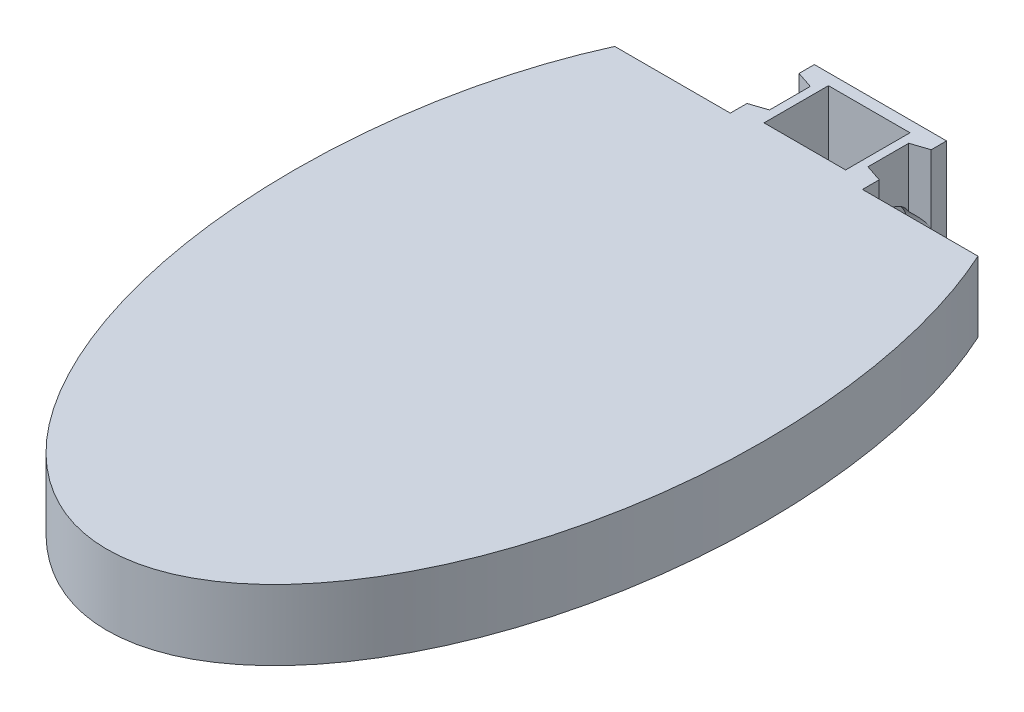
SolidWorks part; units mm, degrees
note: '?' marks a value the reader was unsure of.
ref_plane "Front Plane" through (0, 0, 0) normal (0, 0, 1) x (1, 0, 0)
ref_plane "Top Plane" through (0, 0, 0) normal (0, 1, 0) x (1, 0, 0)
ref_plane "Right Plane" through (0, 0, 0) normal (1, 0, 0) x (0, 0, -1)
sketch "Sketch1" plane through (0, 0, 0) normal (0, 1, 0) x (1, 0, 0)
  line L0 (0, 0) -> (0, 58.7756) construction
  line L1 (0, 0) -> (13.1013, 0) construction
  ellipse E0 centre (0, 0) end of major axis (0, 38.1) minor radius 21.209
  dimension "D1" = 42.418
  dimension "D2" = 76.2
extrude "Boss-Extrude1" add sketch "Sketch1" along normal blind 6.35
sketch "Sketch7" plane through (0, 6.35, 0) normal (0, 1, 0) x (1, 0, 0)
  line L0 (-11.7237, 31.75) -> (11.7237, 31.75)
  ellipse E0 centre (0, 0) end of major axis (0, 38.1) minor radius 21.209 construction
  ellipse E1 centre (0, 0) end of major axis (0, 38.1) minor radius 21.209 (11.7237, 31.75) -> (-11.7237, 31.75) ccw
  dimension "D1" = 31.75
extrude "Cut-Extrude6" cut sketch "Sketch7" against normal through all
sketch "Sketch8" plane through (0, 0, 0) normal (0, -1, 0) x (1, 0, 0)
  line L0 (0, -8.3888) -> (0, -15.4901) construction
  line L1 (5.969, -31.75) -> (5.969, -24.1554)
  line L2 (-11.7237, -31.75) -> (11.7237, -31.75) construction
  line L3 (5.969, -24.1554) -> (25.2503, -24.1554)
  line L4 (25.2503, -24.1554) -> (25.2503, -46.7628)
  line L5 (25.2503, -46.7628) -> (-25.8683, -46.7628)
  line L6 (-25.8683, -46.7628) -> (-25.8683, -24.1554)
  line L7 (-25.8683, -24.1554) -> (-5.969, -24.1554)
  line L8 (-5.969, -24.1554) -> (-5.969, -31.75)
  line L9 (-5.969, -31.75) -> (5.969, -31.75)
  dimension "D1" = 7.5946
  dimension "D2" = 11.938
extrude "Cut-Extrude8" cut sketch "Sketch8" against normal blind 3.81 contours L6 L7 L8 L9 L1 L3 L4 L5
sketch "Sketch9" plane through (5.969, 0, 0) normal (1, 0, 0) x (0, 0, -1)
  line L0 (24.1554, 3.81) -> (24.1554, -2.032)
  line L1 (24.1554, -2.032) -> (24.257, -2.032)
  line L2 (24.257, -2.032) -> (27.305, -4.064)
  line L3 (27.305, -4.064) -> (31.75, -4.064)
  line L4 (31.75, -4.064) -> (31.75, 3.81)
  line L5 (31.75, 3.81) -> (24.1554, 3.81)
  line L6 (31.75, 0) -> (24.1554, 0) construction
  line L7 (31.75, 3.81) -> (31.75, 0) construction
  dimension "D1" = 2.032
  dimension "D2" = 2.032
  dimension "D3" = 3.048
  dimension "D5" = 4.445
extrude "Boss-Extrude2" add sketch "Sketch9" against normal up to surface (11.938 mm away) up to face at (-5.969, 1.905, -27.9527)
sketch "Sketch10" plane through (5.969, 0, 0) normal (1, 0, 0) x (0, 0, -1)
  line L0 (31.75, -4.064) -> (31.75, 3.81) construction
  line L1 (27.305, -4.064) -> (31.75, -4.064) construction
  line L2 (28.0162, -0.635) -> (28.0162, 0.635)
  arc A0 (28.0162, -0.635) -> (28.0162, 0.635) centre (28.0162, 0) ccw
  dimension "D1" = 1.27
  dimension "D2" = 3.7338
  dimension "D3" = 4.064
revolve "Cut-Revolve1" cut sketch "Sketch10" angle 360 about L2
ref_point "Point1"
ref_axis "Axis1" through (5.969, 0, -28.0162) along (-1, 0, 0)?
ref_plane "Plane1" through (0, 0, 0) normal (0, -1, 0) x (-1, 0, 0)
sketch "Sketch14" plane through (0, 0, 0) normal (0, -1, 0) x (-1, 0, 0)
  line L0 (-5.969, 25.6667) -> (-4.064, 25.9842)
  line L1 (-5.969, 24.257) -> (-5.969, 27.305) construction
  line L2 (-5.969, 25.6667) -> (-5.969, 28.0162)
  line L5 (-5.969, 28.0162) -> (-4.064, 28.0162)
  line L7 (0.6045, 28.0162) -> (-1.1769, 28.0162) construction
  line L8 (-5.969, 28.0162) -> (-2.3589, 28.0162) construction
  line L9 (-4.064, 28.0162) -> (-4.064, 25.9842)
  dimension "D1" = 4.699
  dimension "D2" = 4.064
  dimension "D3" = 1.905
revolve "Cut-Revolve2" cut sketch "Sketch14" angle 360 about L7
sketch "Sketch13" plane through (0, 3.81, 0) normal (0, -1, 0) x (1, 0, 0)
  line L4 (16.4016, -24.1554) -> (5.969, -24.1554)
  line L5 (5.969, -24.1554) -> (5.969, -31.75)
  line L6 (5.969, -31.75) -> (11.7237, -31.75)
  line L7 (16.4016, -24.1554) -> (5.969, -24.1554)
  line L8 (5.969, -24.1554) -> (5.969, -31.75)
  line L9 (5.969, -31.75) -> (11.7237, -31.75)
  line L11 (-11.7237, -31.75) -> (-5.969, -31.75)
  line L12 (-5.969, -31.75) -> (-5.969, -24.1554)
  line L13 (-5.969, -24.1554) -> (-16.4016, -24.1554)
  line L14 (-11.7237, -31.75) -> (-5.969, -31.75)
  line L15 (-5.969, -31.75) -> (-5.969, -24.1554)
  line L16 (-5.969, -24.1554) -> (-16.4016, -24.1554)
  ellipse E1 centre (0, 0) end of major axis (0, -38.1) minor radius 21.209 (11.7237, -31.75) -> (16.4016, -24.1554) ccw
  ellipse E2 centre (0, 0) end of major axis (0, -38.1) minor radius 21.209 (11.7237, -31.75) -> (16.4016, -24.1554) ccw
  ellipse E3 centre (0, 0) end of major axis (0, -38.1) minor radius 21.209 (-16.4016, -24.1554) -> (-11.7237, -31.75) ccw
  ellipse E4 centre (0, 0) end of major axis (0, -38.1) minor radius 21.209 (-16.4016, -24.1554) -> (-11.7237, -31.75) ccw
  dimension "D1" = 0
  dimension "D2" = 0
extrude "Cut-Extrude11" cut sketch "Sketch13" against normal through all
sketch "Sketch12" plane through (0, 6.35, -25.4) normal (0, -1, 0) x (-1, 0, 0)
  line L0 (-5.969, 0.2667) -> (-4.445, 0.7747)
  line L2 (-4.445, 0.7747) -> (-4.445, 4.4577)
  line L3 (-4.445, 4.4577) -> (-5.969, 4.9657)
  line L4 (-5.969, 0.2667) -> (-5.969, 4.9657)
  line L5 (-1.6972, 2.6162) -> (-3.104, 2.6162) construction
  line L6 (-5.969, 2.6162) -> (-2.3589, 2.6162) construction
  line L7 (-5.969, -1.2446) -> (-5.969, 6.35) construction
  dimension "D1" = 4.699
  dimension "D2" = 3.683
  dimension "D3" = 1.524
extrude "Cut-Extrude10" cut sketch "Sketch12" along normal up to vertex (70.359 mm away) contours L0 L2 L3 L4
mirror "Mirror1" about plane through (0, 0, 0) normal (1, 0, 0) of "Cut-Revolve2", "Cut-Revolve1", "Cut-Extrude10"
sketch "Sketch16" plane through (0, 6.35, 0) normal (0, 1, 0) x (1, 0, 0)
  line L1 (-3.683, 30.734) -> (3.683, 30.734)
  line L2 (-3.683, 30.734) -> (-3.683, 24.9174)
  line L3 (-3.683, 24.9174) -> (3.683, 24.9174)
  line L4 (3.683, 30.734) -> (3.683, 24.9174)
  line L5 (-5.969, 31.75) -> (5.969, 31.75) construction
  line L6 (-4.445, 26.1747) -> (-4.445, 29.8577) construction
  line L7 (4.445, 26.1747) -> (4.445, 29.8577) construction
  line L8 (-5.969, 24.1554) -> (-16.4016, 24.1554) construction
  dimension "D1" = 1.016
  dimension "D2" = 0.762
  dimension "D3" = 0.762
  dimension "D4" = 0.762
extrude "Cut-Extrude14" cut sketch "Sketch16" against normal up to surface (6.35 mm away)
